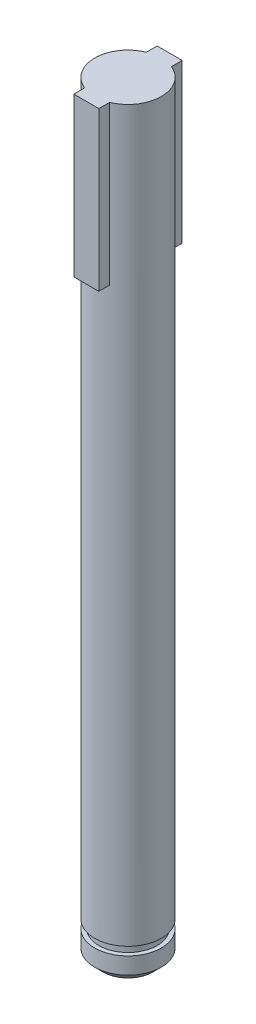
SolidWorks part; units mm, degrees
material "PLA personnalisé"
ref_plane "Plan de face" through (0, 0, 0) normal (0, 0, 1) x (1, 0, 0)
ref_plane "Plan de dessus" through (0, 0, 0) normal (0, 1, 0) x (1, 0, 0)
ref_plane "Plan de droite" through (0, 0, 0) normal (1, 0, 0) x (0, 0, -1)
sketch "Esquisse1" plane through (0, 0, 0) normal (0, 1, 0) x (1, 0, 0)
  circle A0 centre (0, 0) radius 4
  dimension "D1" = 8
extrude "Boss.-Extru.1" add sketch "Esquisse1" along normal blind 8 and the other way blind 83.5
sketch "Esquisse2" plane through (0, 8, 0) normal (0, 1, 0) x (1, 0, 0)
  line L0 (-1.5, 0) -> (1.5, 0)
  line L1 (1.5, 5) -> (1.5, -5)
  line L2 (1.5, -5) -> (-1.5, -5)
  line L3 (-1.5, -5) -> (-1.5, 5)
  line L4 (1.5, 5) -> (-1.5, 5)
  circle M5 centre (0, 0) radius 4
  dimension "D1" = 1.5
  dimension "D2" = 3
  dimension "D3" = 5
extrude "Boss.-Extru.2" add sketch "Esquisse2" against normal blind 19 contours L1 L4 L3 M5 | L3 L2 L1 M5 | L3 L1 L0 M5 | L3 L0 L1 M5 region at (0, 8, -1.953) region at (0, 8, 1.953) region at (0, 8, 4.4487) region at (0, 8, -4.4487)
chamfer "Chanfrein1" distance 1 angle 45 1 edges at (0, -83.5, 4)
sketch "Esquisse3" plane through (0, -83.5, 0) normal (0, -1, 0) x (1, 0, 0)
  circle A0 centre (0, 0) radius 4
  circle A1 centre (0, 0) radius 3.5
  dimension "D1" = 7
extrude "Enlèv. mat.-Extru.1" cut sketch "Esquisse3" against normal blind 1 from offset 3 offset against normal yes
